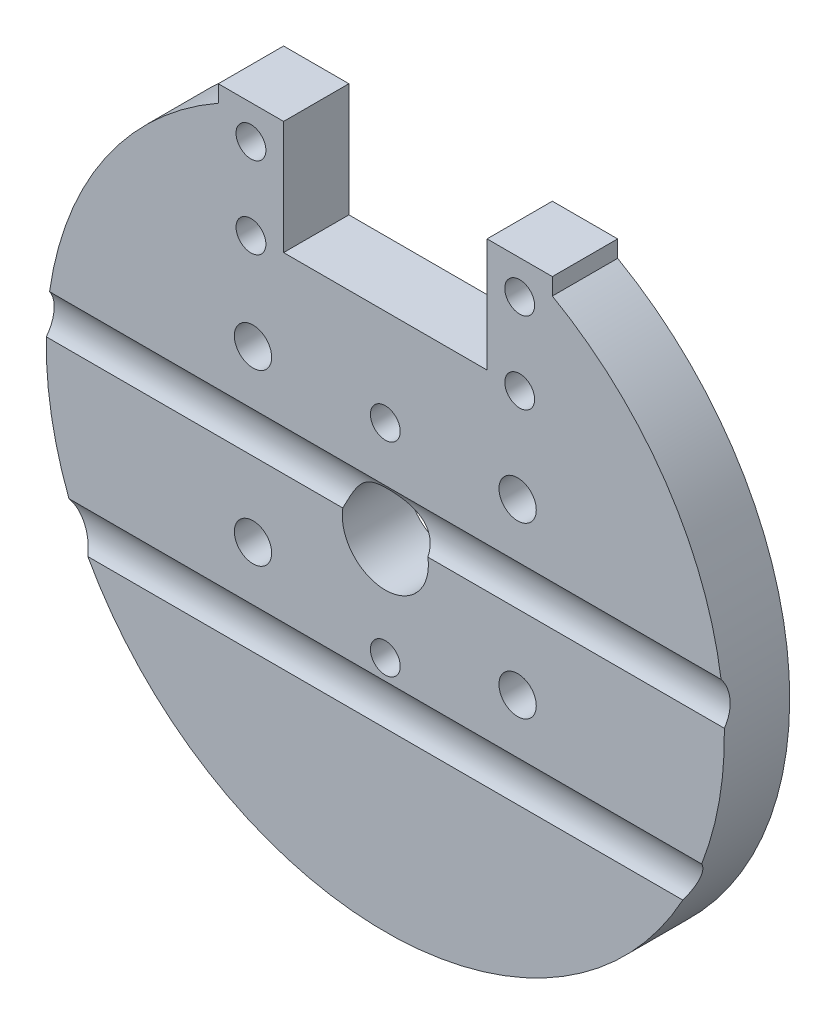
SolidWorks part; units mm, degrees
material "6061 Alloy"
ref_plane "Front Plane" through (0, 0, 0) normal (0, 0, 1) x (1, 0, 0)
ref_plane "Top Plane" through (0, 0, 0) normal (0, 1, 0) x (1, 0, 0)
ref_plane "Right Plane" through (0, 0, 0) normal (1, 0, 0) x (0, 0, -1)
sketch "Sketch1" plane through (0, 0, 0) normal (0, 0, 1) x (1, 0, 0)
  circle A0 centre (0, 0) radius 50
  dimension "D1" = 100
extrude "3/8" add sketch "Sketch1" along normal blind 9.63
sketch "Sketch2" plane through (0, 0, 9.63) normal (0, 0, 1) x (1, 0, 0)
  line L0 (0, 0) -> (0, 50) construction
  line L1 (-1.318, 74.311) -> (-1.318, 76.1424) construction
  line L3 (-15, 46) -> (-15, 29.25)
  line L4 (-15, 29.25) -> (15, 29.25)
  line L5 (15, 46) -> (15, 29.25)
  line L6 (0, 0) -> (0, 50) construction
  line L7 (-15, 37.625) -> (15, 37.625) construction
  line L8 (-30.7361, 76.1424) -> (28.1002, 76.1424)
  line L9 (-30.7361, 76.1424) -> (-30.7361, 46)
  line L10 (-30.7361, 46) -> (-15, 46)
  line L11 (28.1002, 76.1424) -> (28.1002, 46)
  line L12 (15, 46) -> (28.1002, 46)
  line L13 (-30.7361, 61.0712) -> (28.1002, 61.0712) construction
  circle A0 centre (0, 0) radius 50 construction
  point P6 (0, 37.625)
  point P130 (-1.318, 61.0712)
  dimension "D1" = 30
  dimension "D2" = 29.25
  dimension "D3" = 46
extrude "Cut-Extrude1" cut sketch "Sketch2" against normal up to surface (9.63 mm away) up to face at (50, 0, 0)
sketch "Sketch3" plane through (0, 0, 9.63) normal (0, 0, 1) x (1, 0, 0)
  line L1 (-15, 29.25) -> (-24.63, 29.25)
  line L2 (-15, 29.25) -> (-15, 46)
  line L3 (-15, 46) -> (-24.63, 46)
  line L4 (-24.63, 29.25) -> (-24.63, 46)
  line L5 (-19.815, 46) -> (-19.815, 29.25) construction
  line L6 (-15, 37.625) -> (-24.63, 37.625) construction
  line L7 (15, 29.25) -> (24.63, 29.25)
  line L8 (15, 29.25) -> (15, 46)
  line L9 (15, 46) -> (24.63, 46)
  line L10 (24.63, 29.25) -> (24.63, 46)
  line L11 (19.815, 46) -> (19.815, 29.25) construction
  line L12 (15, 37.625) -> (24.63, 37.625) construction
  point P168 (19.815, 37.625)
  point P204 (-19.815, 37.625)
  dimension "D1" = 9.63
  dimension "D2" = 9.63
  dimension "D3" = 46
extrude "Boss-Extrude2" add sketch "Sketch3" against normal up to surface (9.63 mm away) up to face at (0, 24.4167, 0)
sketch "Sketch4" plane through (0, 0, 9.63) normal (0, 0, 1) x (1, 0, 0)
  line L0 (-15, 35) -> (-24.63, 35) construction
  line L2 (-24.63, 46) -> (-24.63, 43.5128) construction
  line L3 (-19.815, 41) -> (-19.815, 35) construction
  line L4 (0, 0) -> (0, 50.3734) construction
  line L5 (-15, 46) -> (-15, 29.25) construction
  circle A0 centre (-19.815, 41) radius 2.2
  circle A1 centre (-19.815, 29) radius 2.2
  circle A2 centre (19.815, 29) radius 2.2
  circle A3 centre (19.815, 41) radius 2.2
  dimension "D1" = 4.4
  dimension "D2" = 6
  dimension "D3" = 35
extrude "M4_through" cut sketch "Sketch4" against normal up to surface (9.63 mm away) up to face at (0, 29.5016, 0)
sketch "Sketch5" plane through (0, 0, 9.63) normal (0, 0, 1) x (1, 0, 0)
  circle A0 centre (0, 0) radius 6.35
  dimension "D1" = 12.7
extrude "Cut-Extrude2" cut sketch "Sketch5" against normal up to surface (9.63 mm away) up to face at (22.015, 41, 0)
sketch "Sketch6" plane through (0, 0, 9.63) normal (0, 0, 1) x (1, 0, 0)
  circle A0 centre (0, 0) radius 15 construction
  circle A1 centre (0, 15) radius 2.2
  circle A2 centre (0, -15) radius 2.2
  point P13 (0, 0)
  dimension "D1" = 30
  dimension "D2" = 4.4
  dimension "D3" = 2
extrude "M4_through2" cut sketch "Sketch6" against normal up to surface (9.63 mm away) up to face at (6.35, 0, 0)
sketch "Sketch7" plane through (0, 0, 9.63) normal (0, 0, 1) x (1, 0, 0)
  line L0 (0, 0) -> (0, 38.8961) construction
  line L1 (-19.51, 15) -> (-19.51, -10) construction
  circle A0 centre (-19.51, 15) radius 2.75
  circle A1 centre (-19.51, -10) radius 2.75
  circle A2 centre (19.51, -10) radius 2.75
  circle A3 centre (19.51, 15) radius 2.75
  circle A4 centre (0, 0) radius 30 construction
  dimension "D2" = 5.5
  dimension "D3" = 25
  dimension "D4" = 60
  dimension "D1" = 19.51
  dimension "D5" = 15
extrude "M5_through" cut sketch "Sketch7" against normal up to surface (9.63 mm away) up to face at (2.2, 15, 0)
chamfer "Chamfer1" distance 2.5 angle 45 4 edges at (22.015, 41, 0) (-17.615, 29, 0) (-17.615, 41, 0) (22.015, 29, 0)
sketch "Sketch8" plane through (0, 0, 0) normal (1, 0, 0) x (0, 0, -1)
  line L0 (-13.63, 4) -> (-9.63, 4) construction
  line L2 (-9.63, 43.5128) -> (-9.63, -50) construction
  line L4 (-13.63, -21) -> (-9.63, -21) construction
  line L6 (-13.63, 4) -> (-13.63, -21) construction
  line L7 (-9.63, 17.75) -> (-9.63, 12.25) construction
  circle A0 centre (-13.63, 4) radius 5
  circle A1 centre (-13.63, -21) radius 5
  point P4 (-9.63, 15)
  dimension "D1" = 10
  dimension "D2" = 4
  dimension "D3" = 11
  dimension "D4" = 25
extrude "Cut-Extrude4" cut sketch "Sketch8" against normal through all and the other way through all
